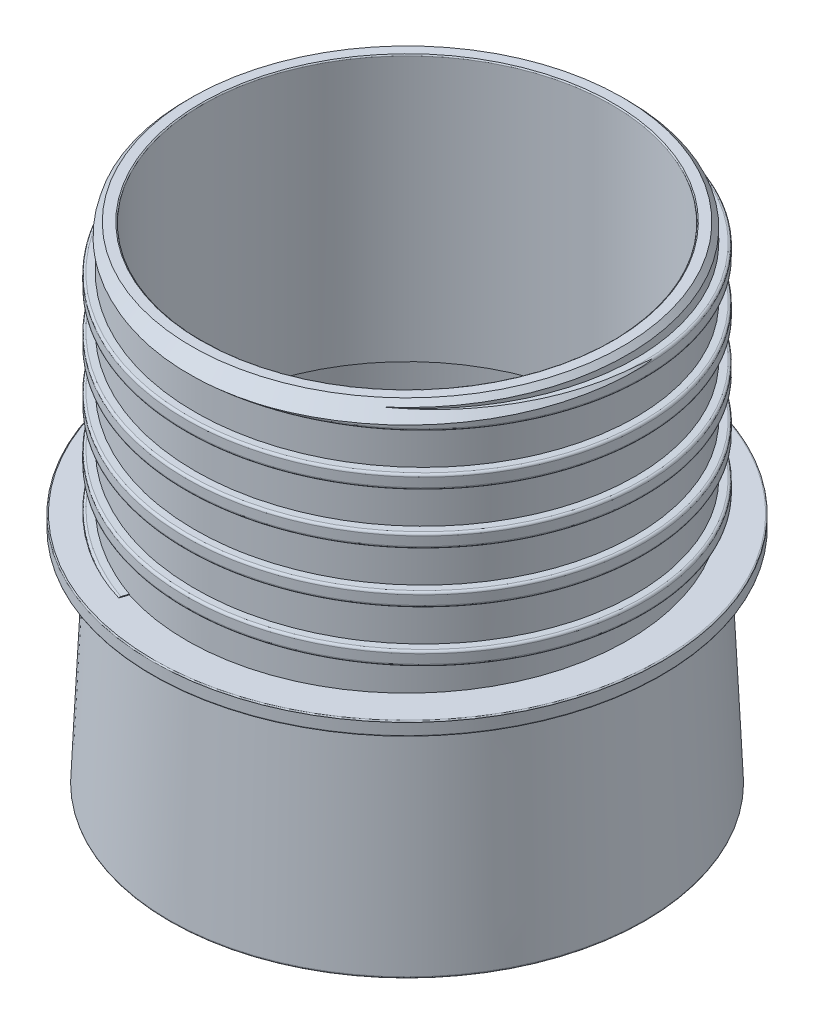
SolidWorks part; units mm, degrees
ref_plane "Front Plane" through (0, 0, 0) normal (0, 0, 1) x (1, 0, 0)
ref_plane "Top Plane" through (0, 0, 0) normal (0, 1, 0) x (1, 0, 0)
ref_plane "Right Plane" through (0, 0, 0) normal (1, 0, 0) x (0, 0, -1)
sketch "Sketch1" plane through (0, 0, 0) normal (0, 0, 1) x (1, 0, 0)
  line L0 (0, 0) -> (0, 59.7) construction
  line L1 (0, 59.7) -> (49.5, 59.7) construction
  line L2 (49.5, 59.7) -> (49.5, 0) construction
  line L3 (49.5, 0) -> (0, 0) construction
  line L4 (49.5, 59.7) -> (46, 59.7)
  line L5 (46, 59.7) -> (46, 0)
  line L6 (49.5, 59.7) -> (49.5, 3.05)
  line L7 (49.5, 3.05) -> (57.2, 3.05)
  line L8 (57.2, 3.05) -> (57.2, 0)
  line L9 (57.2, 0) -> (49.5, 0) construction
  line L10 (57.2, 0) -> (51.2, 0)
  line L11 (51.2, 0) -> (53.45, -49.75)
  line L12 (53.45, -49.75) -> (50.35, -49.75)
  line L13 (50.35, -49.75) -> (48.1, 0)
  line L14 (48.1, 0) -> (46, 0)
  dimension "D1" = 99
  dimension "D2" = 3.5
  dimension "D3" = 7.7
  dimension "D4" = 3.05
  dimension "D5" = 59.7
  dimension "D6" = 52.8
  dimension "D7" = 106.9
  dimension "D8" = 3.1
  dimension "D9" = 6
revolve "Revolve1" add sketch "Sketch1" angle 360 about L0
sketch "Sketch2" plane through (0, 59.7, 0) normal (0, 1, 0) x (1, 0, 0)
  circle A0 centre (0, 0) radius 49.5
  circle A1 centre (0, 0) radius 49.5 construction
curve "Helix/Spiral1" pitch 11.45 height 59.54 turns 5.2
sketch "Sketch4" plane through (0, 0, 0) normal (0, 0, 1) x (1, 0, 0)
  line L0 (-49.5, 59.7) -> (-51.5, 59.7) construction
  line L1 (-49.5, 59.7) -> (-51, 59.7)
  line L4 (-51.5, 59.7) -> (-49.5, 59.7) construction
  line L5 (-51.5, 59.7) -> (-51.5, 62.75) construction
  line L6 (-51.5, 62.75) -> (-49.5, 62.75) construction
  line L7 (-49.5, 59.7) -> (-49.5, 62.75)
  line L8 (-51.5, 60.2) -> (-51.5, 62.25)
  line L9 (-51, 62.75) -> (-49.5, 62.75)
  arc A0 (-51, 59.7) -> (-51.5, 60.2) centre (-51, 60.2) cw
  arc A1 (-51.5, 62.25) -> (-51, 62.75) centre (-51, 62.25) cw
  dimension "D3" = 0.5
  dimension "D1" = 2
  dimension "D2" = 3.05
sweep "Sweep1" add profiles "Sketch4" path "Helix/Spiral1"
sketch "Sketch5" plane through (0, 0, 0) normal (0, 0, 1) x (1, 0, 0)
  line L0 (48.4, 59.7) -> (53.4, 54.7)
  line L1 (49.5, 59.7) -> (-49.5, 59.7) construction
  line L2 (53.4, 54.7) -> (58.4, 54.7)
  line L3 (58.4, 54.7) -> (58.4, 64.7)
  line L4 (58.4, 64.7) -> (48.4, 64.7)
  line L5 (48.4, 64.7) -> (48.4, 59.7)
  line L6 (49.5, 57.025) -> (49.5, 59.7) construction
  line L7 (0, 0) -> (0, 70.2081) construction
  dimension "D1" = 5
  dimension "D2" = 1.1
  dimension "D3" = 45
  dimension "D4" = 5
  dimension "D5" = 10
revolve "Cut-Revolve1" cut sketch "Sketch5" angle 360 about L7
fillet "Fillet1" radius 0.25 3 edges at (0, 59.7, -46) (0, 0, -57.2) (0, 3.05, -57.2)
fillet "Fillet2" radius 0.4 2 edges at (0, -49.75, -53.45) (0, -49.75, -50.35)
